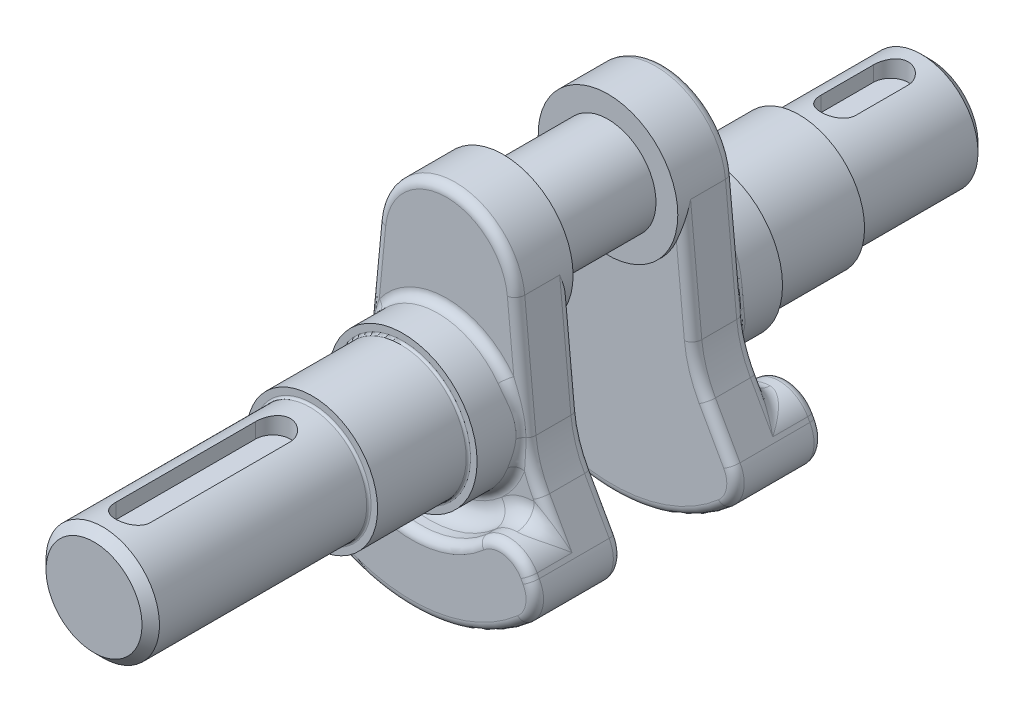
SolidWorks part; units mm, degrees
ref_plane "Přední rovina" through (0, 0, 0) normal (0, 0, 1) x (1, 0, 0)
ref_plane "Horní rovina" through (0, 0, 0) normal (0, 1, 0) x (1, 0, 0)
ref_plane "Pravá rovina" through (0, 0, 0) normal (1, 0, 0) x (0, 0, -1)
other "Těžiště"
sketch "Skica1" plane through (0, 0, 0) normal (0, 0, 1) x (1, 0, 0)
  line L1 (18.5, 0) -> (15.9253, 26.5447)
  line L3 (-15.9253, 26.5447) -> (-18.5, 0)
  line L5 (18.5, 0) -> (-18.5, 0) construction
  line L6 (0, 0) -> (0, -24.9199) construction
  line L7 (-30, -24.9199) -> (30, -24.9199) construction
  line L8 (30, -24.9199) -> (21.6354, -10)
  line L9 (-30, -24.9199) -> (-21.6354, -10)
  line L10 (-21.6354, -10) -> (21.6354, -10) construction
  circle A0 centre (0, 0) radius 25 construction
  circle A1 centre (0, 25) radius 11
  circle A2 centre (0, 25) radius 16
  arc A3 (-30, -24.9199) -> (30, -24.9199) centre (0, 0) ccw
  arc A4 (-18.5, 0) -> (-21.6354, -10) centre (-43.8599, 2.4598) cw
  arc A5 (18.5, 0) -> (21.6354, -10) centre (43.8599, 2.4598) ccw
  arc A6 (-21.1374, -9.0669) -> (21.1374, -9.0669) centre (0, 0) ccw
  circle A7 centre (0, 0) radius 41 construction
  point P12 (0, -10)
  dimension "D1" = 50
  dimension "D2" = 22
  dimension "D3" = 5
  dimension "D5" = 32
  dimension "D6" = 60
  dimension "D8" = 16
  dimension "D9" = 2
  dimension "D4" = 37
  dimension "D7" = 10
extrude "Přidat vysunutím1" add sketch "Skica1" along normal mid plane 50 contours A1 | A2 A1 | L9 A6 L8 A5 L1 A2 L3 A4 | A6 L9 A3 L8 region at (0, -3.7904, 0) region at (15.5293, 25.7514, 0) region at (0, -26.5728, 0) region at (0, 25, 0)
extrude "Přidat vysunutím2" add sketch "Skica1<3>" along normal mid plane 66 contours A6 L9 A3 L8 region at (0, -26.5728, 0)
sketch "Skica1<3>" plane through (0, 0, 0) normal (0, 0, 1) x (1, 0, 0) same geometry as "Skica1"
extrude "Odebrat vysunutím1" cut sketch "Skica1<4>" against normal mid plane 26 contours A6 L9 A3 L8 | L9 A6 L8 A5 L1 A2 L3 A4 region at (0, -3.7904, 0) region at (0, -26.5728, 0)
sketch "Skica1<4>" plane through (0, 0, 0) normal (0, 0, 1) x (1, 0, 0) same geometry as "Skica1"
extrude "Odebrat vysunutím2" cut sketch "Skica1<5>" against normal mid plane 24 contours A2 A1 region at (15.5293, 25.7514, 0)
sketch "Skica1<5>" plane through (0, 0, 0) normal (0, 0, 1) x (1, 0, 0) same geometry as "Skica1"
fillet "Zaoblit1" radius 7.5 8 edges at (30, -24.9199, 23) (-30, -24.9199, 23) (30, -24.9199, -23) (-30, -24.9199, -23) (21.1374, -9.0669, -29) (21.1374, -9.0669, 29) (-21.1374, -9.0669, 29) (-21.1374, -9.0669, -29)
fillet "Zaoblit2" radius 2 48 edges at (0, -23, -33) (0, -23, 33) (0, -39, 33) (-28.1193, -24.9936, 33) (28.1193, -24.9936, 33) (-28.1193, -24.9936, -33) (28.1193, -24.9936, -33) (0, -39, -33) (0, 41, -25) (-17.2126, 13.2723, -25) (-19.548, -5.1629, -25) (24.2029, -14.5796, -25) (19.548, -5.1629, -25) (17.2126, 13.2723, -25) (0, 41, 25) (-17.2126, 13.2723, 25) (-19.548, -5.1629, 25) (-24.2029, -14.5796, 25) (24.2029, -14.5796, 25) (19.548, -5.1629, 25) (17.2126, 13.2723, 25) (-24.2029, -14.5796, -25) (17.2126, 13.2723, 13) (19.548, -5.1629, 13) (24.4529, -15.0256, 13) (28.1193, -24.9936, 13) (0, -39, 13) (-28.1193, -24.9936, 13) (-17.2126, 13.2723, 13) (-19.548, -5.1629, 13) (-17.2126, 13.2723, -13) (-19.548, -5.1629, -13) (-24.4529, -15.0256, -13) (17.2126, 13.2723, -13) (19.548, -5.1629, -13) (24.4529, -15.0256, -13) (28.1193, -24.9936, -13) (0, -39, -13) (-24.4529, -15.0256, 13) (-28.1193, -24.9936, -13) (-27.0204, -19.6052, 33) (27.0204, -19.6052, 33) (-27.0204, -19.6052, -33) (27.0204, -19.6052, -33) (-21.4776, -15.4316, 33) (21.4776, -15.4316, 33) (-21.4776, -15.4316, -33) (21.4776, -15.4316, -33)
fillet "Zaoblit3" radius 4 10 edges at (0, -23, 25) (0, -23, -25) (23.8633, -16.2666, 24.7966) (18.691, -15.4861, 25) (-23.8633, -16.2666, 24.7966) (-18.691, -15.4861, 25) (23.8633, -16.2666, -24.7966) (18.691, -15.4861, -25) (-23.8633, -16.2666, -24.7966) (-18.691, -15.4861, -25)
sketch "Skica2" plane through (0, 0, 0) normal (1, 0, 0) x (0, 0, -1)
  line L0 (-46.8918, 0) -> (49.3477, 0) construction
  line L1 (-23, 0) -> (-23, 17)
  line L3 (-23, 17) -> (-35, 17)
  line L4 (-35, 17) -> (-35, 15)
  line L5 (-35, 15) -> (-55.8, 15)
  line L10 (-55.8, 15) -> (-55.8, 13)
  line L11 (-55.8, 13) -> (-105.8, 13)
  line L12 (-105.8, 13) -> (-105.8, 0)
  line L13 (-105.8, 0) -> (-23, 0)
  line L23 (-33, -21.0292) -> (-33, -27.8602) construction
  line L25 (23, 0) -> (23, 17)
  line L26 (23, 0) -> (23, 26.5447) construction
  line L27 (23, 17) -> (35, 17)
  line L28 (35, 17) -> (35, 15)
  line L29 (35, 15) -> (55.8, 15)
  line L34 (55.8, 15) -> (55.8, 13)
  line L35 (55.8, 13) -> (85.8, 13)
  line L36 (85.8, 13) -> (85.8, 0)
  line L37 (85.8, 0) -> (23, 0)
  point P12 (-55.4429, 15)
  point P20 (0, 0)
  dimension "D1" = 34
  dimension "D2" = 2
  dimension "D3" = 30
  dimension "D4" = 30
  dimension "D5" = 20.8
  dimension "D9" = 26
  dimension "D10" = 50
revolve "Rotovat1" add sketch "Skica2" angle 360 about L0
ref_plane "Rovina1" through (0, 13, 0) normal (0, 1, 0) x (1, 0, 0)
sketch "Skica3" plane through (0, 13, 0) normal (0, 1, 0) x (1, 0, 0)
  line L0 (0, -64.8) -> (0, -96.8) construction
  line L1 (4, -64.8) -> (4, -96.8)
  line L2 (-4, -64.8) -> (-4, -96.8)
  line L4 (-13, -105.8) -> (13, -105.8) construction
  line L5 (0, 64.8) -> (0, 76.8) construction
  line L6 (-4, 64.8) -> (-4, 76.8)
  line L7 (4, 64.8) -> (4, 76.8)
  line L9 (13, 85.8) -> (-13, 85.8) construction
  arc A0 (4, -64.8) -> (-4, -64.8) centre (0, -64.8) ccw
  arc A1 (-4, -96.8) -> (4, -96.8) centre (0, -96.8) ccw
  arc A2 (-4, 64.8) -> (4, 64.8) centre (0, 64.8) ccw
  arc A3 (4, 76.8) -> (-4, 76.8) centre (0, 76.8) ccw
  point P3 (0, -80.8)
  point P12 (0, 70.8)
  dimension "D2" = 40
  dimension "D3" = 5
  dimension "D4" = 5
  dimension "D5" = 20
  dimension "D1" = 8
extrude "Odebrat vysunutím3" cut sketch "Skica3" against normal blind 4.1
fillet "Zaoblit5" radius 0.5 4 edges at (15, 0, 35) (13, 0, 55.8) (13, 0, -55.8) (15, 0, -35)
chamfer "Zkosení2" distance 2 angle 45 2 edges at (13, 0, -85.8) (13, 0, 105.8)
fillet "Zaoblit6" radius 2 12 edges at (0, -17, 25) (16.7606, 2.8427, 24.9248) (-16.7606, 2.8427, -24.9248) (0, -17, -25) (0, 17, 25) (0, 17, -25)
